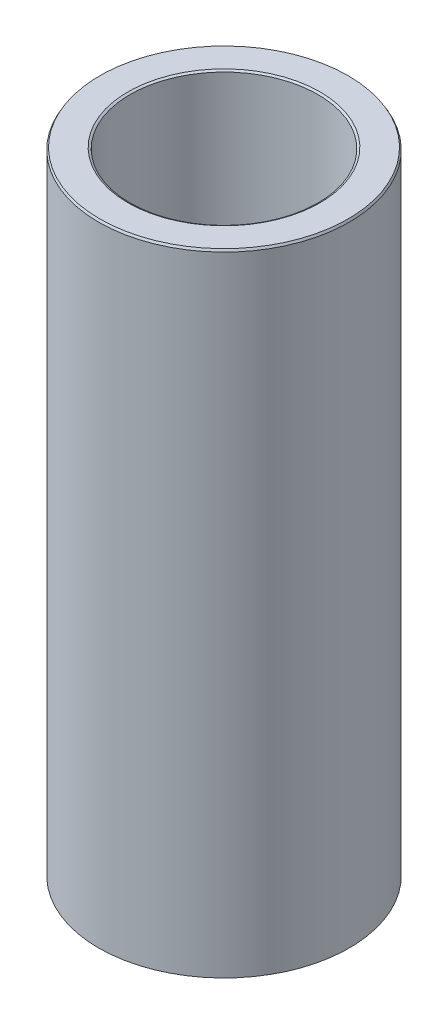
SolidWorks part; units mm, degrees
ref_plane "Front Plane" through (0, 0, 0) normal (0, 0, 1) x (1, 0, 0)
ref_plane "Top Plane" through (0, 0, 0) normal (0, 1, 0) x (1, 0, 0)
ref_plane "Right Plane" through (0, 0, 0) normal (1, 0, 0) x (0, 0, -1)
sketch "Sketch1" plane through (0, 0, 0) normal (0, 1, 0) x (1, 0, 0)
  circle A0 centre (0, 0) radius 55
  dimension "SLEEVE_OD" = 110
extrude "Boss-Extrude1" add sketch "Sketch1" along normal blind 277.2996
sketch "Sketch2" plane through (0, 0, 0) normal (0, 1, 0) x (1, 0, 0)
  circle A0 centre (0, 0) radius 41.2249
  dimension "BORE_D" = 82.4497
extrude "Cut-Extrude1" cut sketch "Sketch2" along normal through all
chamfer "Chamfer1" distance 0.9357 angle 30 4 edges at (0, 277.2996, 41.2249) (0, 0, 41.2249) (0, 0, 55) (0, 277.2996, 55) first distance on face at (0, 277.2996, 41.2249) first distance on face at (0, 0, 41.2249) first distance on face at (0, 277.2996, 55)
